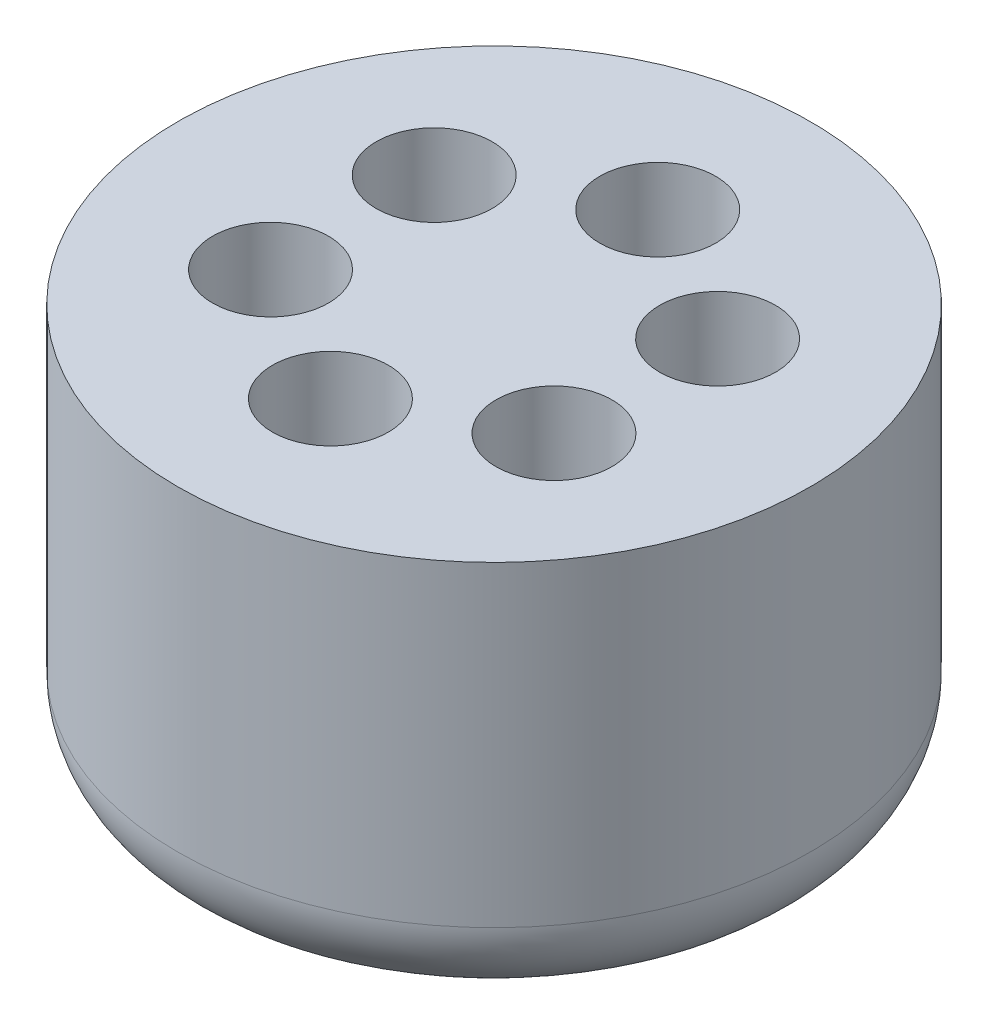
SolidWorks part; units mm, degrees
ref_plane "Front Plane" through (0, 0, 0) normal (0, 0, 1) x (1, 0, 0)
ref_plane "Top Plane" through (0, 0, 0) normal (0, 1, 0) x (1, 0, 0)
ref_plane "Right Plane" through (0, 0, 0) normal (1, 0, 0) x (0, 0, -1)
sketch "Sketch1" plane through (0, 0, 0) normal (0, 1, 0) x (1, 0, 0)
  circle A0 centre (0, 0) radius 30
extrude "Boss-Extrude1" add sketch "Sketch1" along normal blind 38
sketch "Sketch2" plane through (0, 38, 0) normal (0, 1, 0) x (1, 0, 0)
  circle A0 centre (0, 15.52) radius 5.5
  circle A2 centre (-13.4407, 7.76) radius 5.5
  circle A3 centre (-13.4407, -7.76) radius 5.5
  circle A4 centre (0, -15.52) radius 5.5
  circle A5 centre (13.4407, -7.76) radius 5.5
  circle A6 centre (13.4407, 7.76) radius 5.5
  dimension "D1" = 15.52
extrude "Cut-Extrude1" cut sketch "Sketch2" against normal blind 32
fillet "Fillet1" radius 8 1 edges at (0, 0, 30)
extrude "Cut-Extrude2" cut sketch "Sketch2<3>" against normal blind 35
sketch "Sketch2<3>" plane through (0, 38, 0) normal (0, 1, 0) x (1, 0, 0) same geometry as "Sketch2"
